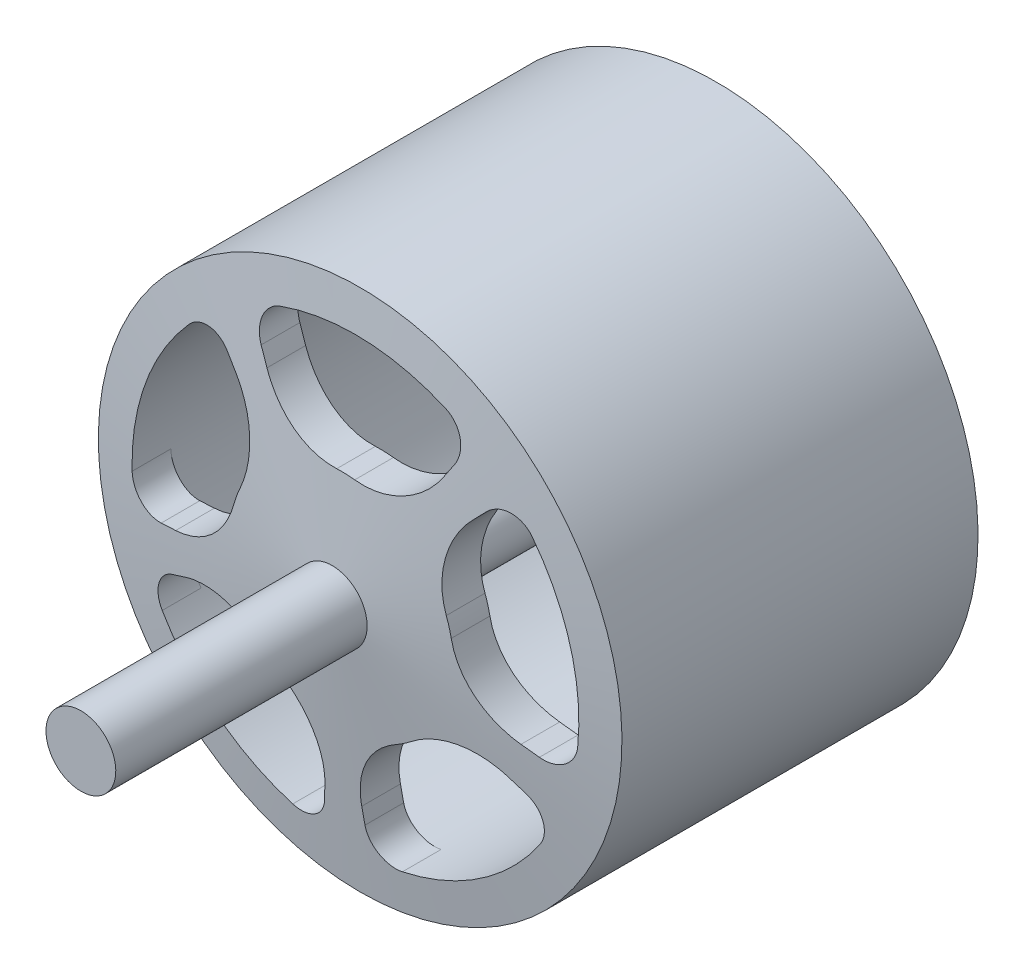
SolidWorks part; units mm, degrees
material "AISI 1020 Steel, Cold Rolled"
ref_plane "Front Plane" through (0, 0, 0) normal (0, 0, 1) x (1, 0, 0)
ref_plane "Top Plane" through (0, 0, 0) normal (0, 1, 0) x (1, 0, 0)
ref_plane "Right Plane" through (0, 0, 0) normal (1, 0, 0) x (0, 0, -1)
sketch "Sketch1" plane through (0, 0, 0) normal (1, 0, 0) x (0, 0, -1)
  line L0 (0, 0) -> (-45.5, 0) construction
  line L1 (-45.5, 0) -> (-45.5, 2.5)
  line L2 (-45.5, 2.5) -> (-27.5, 2.5)
  line L3 (-27.5, 2.5) -> (-25.5, 18.75)
  line L4 (-25.5, 18.75) -> (0, 18.75)
  line L5 (0, 18.75) -> (0, 0) construction
  line L6 (-45.5, 0) -> (0, 0)
  line L8 (-23.0677, 16) -> (0, 16)
  line L9 (0, 16) -> (0, 18.75)
  line L10 (-27.5, 2.5) -> (-24.7706, 2.1641) construction
  line L12 (7.7, 2.5) -> (-24.7292, 2.5)
  line L13 (-23.0677, 16) -> (-24.7706, 2.1641) construction
  line L14 (-23.0677, 16) -> (-24.7292, 2.5)
  line L15 (7.7, 2.5) -> (7.7, 0)
  line L16 (7.7, 0) -> (0, 0)
  dimension "D1" = 18.75
  dimension "D2" = 2.5
  dimension "D3" = 18
  dimension "D4" = 45.5
  dimension "D5" = 20
  dimension "D6" = 16
  dimension "D7" = 53.2
revolve "Revolve1" add sketch "Sketch1" angle 360 about L6
sketch "Sketch2" plane through (0, 0, 0) normal (0, 0, 1) x (1, 0, 0)
  line L0 (0, 0) -> (8.497, 13.5573) construction
  line L1 (0, 0) -> (-7.4924, 14.1373) construction
  line L2 (-6.4886, 12.2433) -> (-5.9233, 11.1765)
  line L3 (7.3587, 11.741) -> (6.7175, 10.718)
  circle A0 centre (0, 0) radius 16 construction
  arc A1 (-5.396, 15.0627) -> (6.4731, 14.6321) centre (0, 0) cw
  circle A2 centre (0, 0) radius 8 construction
  arc A3 (-0.3553, 7.9921) -> (0.9334, 7.9454) centre (0, 0) cw
  arc A4 (6.4731, 14.6321) -> (7.3587, 11.741) centre (5.664, 12.8031) cw
  arc A5 (-6.4886, 12.2433) -> (-5.396, 15.0627) centre (-4.7215, 13.1798) cw
  arc A6 (0.9334, 7.9454) -> (6.7175, 10.718) centre (1.6335, 13.9044) ccw
  arc A7 (-0.3553, 7.9921) -> (-5.9233, 11.1765) centre (-0.6218, 13.9862) cw
  point P18 (4.2485, 6.7786)
  point P21 (-3.7462, 7.0687)
  dimension "D1" = 32
  dimension "D3" = 16
  dimension "D4" = 2
  dimension "D5" = 6
  dimension "D2" = 60
extrude "Cut-Extrude1" cut sketch "Sketch2" along normal through all contours A3 A6 L3 A4 A1 A5 L2 A7
pattern_circular "CirPattern1" count 5 over 360 about axis through (0, 0, 45.5) along (0, 0, 1) of "Cut-Extrude1" reverse direction yes
